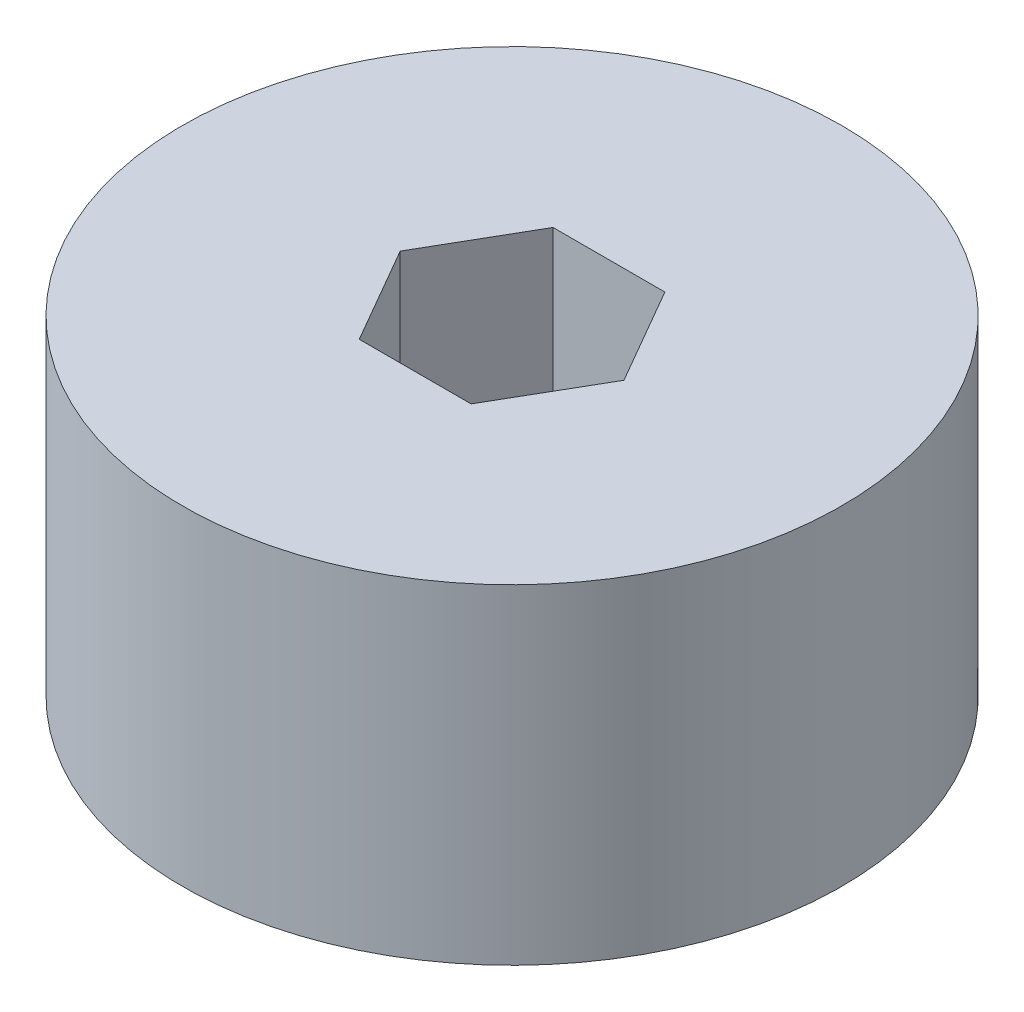
SolidWorks part; units mm, degrees
material "Custom Plastic"
ref_plane "Front Plane" through (0, 0, 0) normal (0, 0, 1) x (1, 0, 0)
ref_plane "Top Plane" through (0, 0, 0) normal (0, 1, 0) x (1, 0, 0)
ref_plane "Right Plane" through (0, 0, 0) normal (1, 0, 0) x (0, 0, -1)
sketch "Sketch1" plane through (0, 0, 0) normal (0, 1, 0) x (1, 0, 0)
  circle A0 centre (0, 0) radius 4.7625
  dimension "D1" = 9.525
extrude "Boss-Extrude1" add sketch "Sketch1" along normal blind 4.7625
sketch "Sketch2" plane through (0, 0, 0) normal (0, -1, 0) x (1, 0, 0)
  line L1 (0.8083, 1.4) -> (-0.8083, 1.4)
  line L2 (-0.8083, 1.4) -> (-1.6166, 0)
  line L3 (-1.6166, 0) -> (-0.8083, -1.4)
  line L4 (-0.8083, -1.4) -> (0.8083, -1.4)
  line L5 (0.8083, -1.4) -> (1.6166, 0)
  line L6 (1.6166, 0) -> (0.8083, 1.4)
  circle A0 centre (0, 0) radius 1.4 construction
  dimension "D1" = 2.8
extrude "Cut-Extrude1" cut sketch "Sketch2" against normal through all
